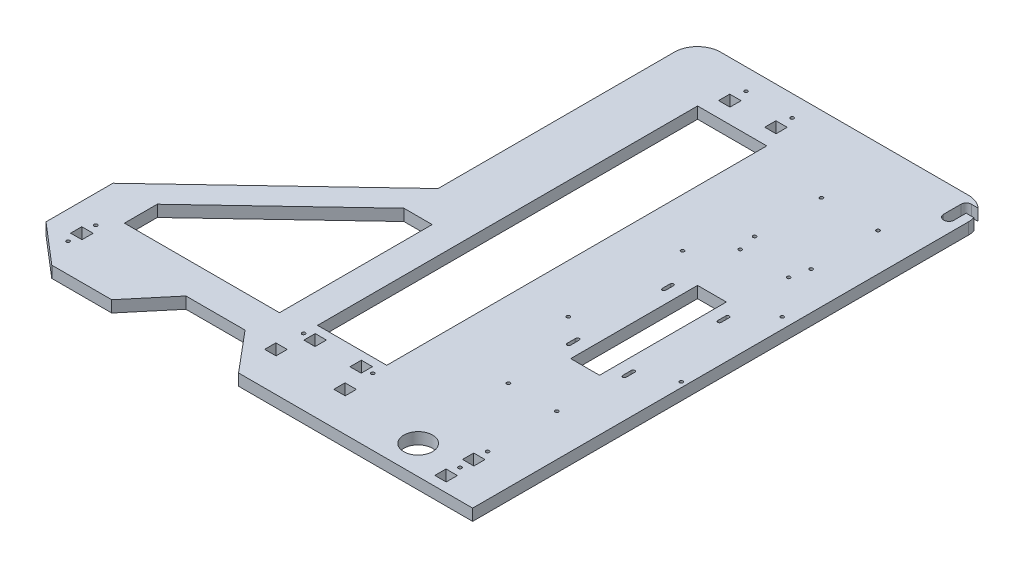
SolidWorks part; units mm, degrees
ref_plane "Front Plane" through (0, 0, 0) normal (0, 0, 1) x (1, 0, 0)
ref_plane "Top Plane" through (0, 0, 0) normal (0, 1, 0) x (1, 0, 0)
ref_plane "Right Plane" through (0, 0, 0) normal (1, 0, 0) x (0, 0, -1)
sketch "Sketch1" plane through (0, 0, 0) normal (0, 1, 0) x (1, 0, 0)
  line L0 (0, 0) -> (-235, 0)
  line L1 (-235, 0) -> (-235, -225)
  line L2 (-235, -225) -> (-380, -362)
  line L3 (-380, -362) -> (-380, -420)
  line L4 (-380, -420) -> (-345, -450)
  line L5 (-345, -450) -> (-293, -450)
  line L6 (-293, -450) -> (-263.6315, -415)
  line L7 (-263.6315, -415) -> (-212.3685, -415)
  line L8 (-212.3685, -415) -> (-183, -450)
  line L9 (-183, -450) -> (0, -450)
  line L10 (0, 0) -> (0, -450)
  line L12 (-293, -450) -> (-183, -450) construction
  dimension "D3" = 235
  dimension "D5" = 58
  dimension "D13" = 190
  dimension "D7" = 35
  dimension "D15" = 52
  dimension "D12" = 30
  dimension "D10" = 35
  dimension "D6" = 380
  dimension "D4" = 450
  dimension "D2" = 50
  dimension "D8" = 50
  dimension "D9" = 110
extrude "Boss-Extrude1" add sketch "Sketch1" along normal blind 10
sketch "Sketch16" plane through (0, 10, 0) normal (0, 1, 0) x (1, 0, 0)
  line L0 (0, -450) -> (20, -450)
  line L1 (20, -450) -> (20, 0)
  line L2 (20, 0) -> (0, 0)
  line L3 (0, 0) -> (0, -450)
  dimension "D1" = 20
  dimension "D2" = 90
extrude "Boss-Extrude2" add sketch "Sketch16" against normal through all
sketch "Sketch2" plane through (0, 10, 0) normal (0, 1, 0) x (1, 0, 0)
  line L0 (-235, -225) -> (-235, -415) construction
  line L1 (-263.6315, -415) -> (-212.3685, -415) construction
  line L2 (-345, -450) -> (-345, -328.931) construction
  line L3 (-235, -225) -> (-380, -362) construction
  line L4 (-345, -358.5097) -> (-235, -254.5787)
  line L5 (-235, -254.5787) -> (-210.5, -254.5787)
  line L6 (-210.5, -254.5787) -> (-210.5, -387)
  line L7 (-210.5, -387) -> (-345, -387)
  line L8 (-345, -387) -> (-345, -358.5097)
  line L9 (0, -450) -> (0, 0) construction
  line L10 (-184.5, -380) -> (-124.5, -380)
  line L11 (-184.5, -380) -> (-184.5, -50.425)
  line L12 (-184.5, -50.425) -> (-124.5, -50.425)
  line L13 (-124.5, -380) -> (-124.5, -50.425)
  line L14 (-124.5, -392.1) -> (-184.5, -392.1) construction
  line L15 (-16, -450) -> (-16, 0) construction
  line L16 (20, 0) -> (-235, 0) construction
  line L17 (-355.9, -440.6571) -> (-355.9, -339.2297) construction
  line L18 (-20.925, -441.85) -> (-11.075, -441.85)
  line L19 (-20.925, -441.85) -> (-20.925, -432.15)
  line L20 (-20.925, -432.15) -> (-11.075, -432.15)
  line L21 (-11.075, -441.85) -> (-11.075, -432.15)
  line L22 (-20.925, -441.85) -> (-11.075, -432.15) construction
  line L23 (-20.925, -432.15) -> (-11.075, -441.85) construction
  line L24 (-20.925, -417.85) -> (-11.075, -417.85)
  line L25 (-20.925, -417.85) -> (-20.925, -408.15)
  line L26 (-20.925, -408.15) -> (-11.075, -408.15)
  line L27 (-11.075, -417.85) -> (-11.075, -408.15)
  line L28 (-20.925, -417.85) -> (-11.075, -408.15) construction
  line L29 (-20.925, -408.15) -> (-11.075, -417.85) construction
  line L30 (-380, -420) -> (-345, -450) construction
  line L32 (-350.975, -408.15) -> (-360.825, -408.15)
  line L33 (-350.975, -408.15) -> (-350.975, -417.85)
  line L34 (-350.975, -417.85) -> (-360.825, -417.85)
  line L35 (-360.825, -408.15) -> (-360.825, -417.85)
  line L36 (-350.975, -408.15) -> (-360.825, -417.85) construction
  line L37 (-350.975, -417.85) -> (-360.825, -408.15) construction
  line L38 (-183, -450) -> (20, -450) construction
  line L39 (-183, -450) -> (20, -450) construction
  line L40 (-173.749, -32.425) -> (-113.749, -32.425) construction
  line L41 (-154.5, -50.425) -> (-154.5, -32.425) construction
  line L42 (-179.425, -27.575) -> (-169.575, -27.575)
  line L43 (-179.425, -27.575) -> (-179.425, -37.275)
  line L44 (-179.425, -37.275) -> (-169.575, -37.275)
  line L45 (-169.575, -27.575) -> (-169.575, -37.275)
  line L46 (-179.425, -27.575) -> (-169.575, -37.275) construction
  line L47 (-179.425, -37.275) -> (-169.575, -27.575) construction
  line L48 (-129.575, -37.275) -> (-139.425, -27.575) construction
  line L49 (-129.575, -27.575) -> (-139.425, -37.275) construction
  line L50 (-139.425, -27.575) -> (-139.425, -37.275)
  line L51 (-129.575, -37.275) -> (-139.425, -37.275)
  line L52 (-129.575, -27.575) -> (-129.575, -37.275)
  line L53 (-129.575, -27.575) -> (-139.425, -27.575)
  line L54 (-174.5, -32.425) -> (-174.5, -18.425) construction
  line L55 (-134.5, -32.425) -> (-134.5, -18.425) construction
  line L56 (-154.5, -380) -> (-154.5, -450) construction
  line L57 (-174.5, -392.1) -> (-134.5, -392.1) construction
  line L58 (-129.65, -397.025) -> (-139.35, -387.175) construction
  line L59 (-179.35, -387.175) -> (-169.65, -387.175)
  line L60 (-179.35, -387.175) -> (-179.35, -397.025)
  line L61 (-179.35, -397.025) -> (-169.65, -397.025)
  line L62 (-169.65, -387.175) -> (-169.65, -397.025)
  line L63 (-179.35, -387.175) -> (-169.65, -397.025) construction
  line L64 (-179.35, -397.025) -> (-169.65, -387.175) construction
  line L65 (-129.65, -387.175) -> (-139.35, -397.025) construction
  line L66 (-139.35, -387.175) -> (-139.35, -397.025)
  line L67 (-129.65, -397.025) -> (-139.35, -397.025)
  line L68 (-129.65, -387.175) -> (-129.65, -397.025)
  line L69 (-129.65, -387.175) -> (-139.35, -387.175)
  line L70 (-119.575, -420.95) -> (-129.425, -411.25) construction
  line L71 (-189.425, -411.25) -> (-179.575, -411.25)
  line L72 (-189.425, -411.25) -> (-189.425, -420.95)
  line L73 (-189.425, -420.95) -> (-179.575, -420.95)
  line L74 (-179.575, -411.25) -> (-179.575, -420.95)
  line L75 (-189.425, -411.25) -> (-179.575, -420.95) construction
  line L76 (-189.425, -420.95) -> (-179.575, -411.25) construction
  line L77 (-119.575, -411.25) -> (-129.425, -420.95) construction
  line L78 (-129.425, -411.25) -> (-129.425, -420.95)
  line L79 (-119.575, -420.95) -> (-129.425, -420.95)
  line L80 (-119.575, -411.25) -> (-119.575, -420.95)
  line L81 (-119.575, -411.25) -> (-129.425, -411.25)
  line L82 (-360.825, -408.15) -> (-11.075, -408.15) construction
  circle A0 centre (-16, -425) radius 1.45
  circle A1 centre (-16, -401) radius 1.45
  circle A2 centre (-355.9, -425) radius 1.45
  circle A3 centre (-355.9, -401) radius 1.45
  circle A4 centre (-174.5, -18.425) radius 1.45
  circle A5 centre (-134.5, -18.425) radius 1.45
  circle A6 centre (-124.5, -392.1) radius 1.45
  circle A7 centre (-184.5, -392.1) radius 1.45
  point P25 (-16, -437)
  point P30 (-16, -413)
  point P44 (-355.9, -413)
  point P61 (-174.5, -32.425)
  point P72 (-134.5, -32.425)
  point P85 (-174.5, -392.1)
  point P94 (-134.5, -392.1)
  point P95 (-184.5, -416.1)
  point P104 (-124.5, -416.1)
  point P105 (-154.5, -392.1)
  dimension "D13" = 2.9
  dimension "D14" = 2.9
  dimension "D23" = 2.9
  dimension "D24" = 2.9
  dimension "D31" = 2.9
  dimension "D37" = 2.9
  dimension "D1" = 21.5
  dimension "D2" = 28
  dimension "D3" = 24.5
  dimension "D4" = 60
  dimension "D7" = 26
  dimension "D8" = 9.7
  dimension "D9" = 9.85
  dimension "D10" = 9.85
  dimension "D11" = 9.7
  dimension "D12" = 24
  dimension "D15" = 24
  dimension "D19" = 9.85
  dimension "D20" = 9.7
  dimension "D26" = 12
  dimension "D27" = 9.85
  dimension "D28" = 9.7
  dimension "D33" = 9.7
  dimension "D38" = 9.85
  dimension "D39" = 9.7
  dimension "D41" = 24
  dimension "D34" = 30
  dimension "D36" = 12.1
  dimension "D30" = 18
  dimension "D29" = 40
  dimension "D17" = 13
  dimension "D32" = 14
  dimension "D35" = 20
  dimension "D16" = 12
  dimension "D21" = 90
  dimension "D25" = 24
  dimension "D5" = 359.75
  dimension "D22" = 349.75
  dimension "D40" = 30
  dimension "D6" = 70
  dimension "D42" = 0
  dimension "D43" = 0
  dimension "D18" = 16
  dimension "D44" = 9.85
extrude "Cut-Extrude1" cut sketch "Sketch2" against normal through all
fillet "Fillet1" radius 20 2 edges at (-235, 5, 0) (20, 5, 0)
sketch "Sketch11" plane through (0, 10, 0) normal (0, 1, 0) x (1, 0, 0)
  line L0 (-124.5, -215.2125) -> (20, -215.2125) construction
  line L1 (20, -450) -> (20, -20) construction
  line L3 (-52.25, -215.2125) -> (-52.25, -450) construction
  line L6 (-124.5, -380) -> (-124.5, -50.425) construction
  line L8 (-183, -450) -> (20, -450) construction
  circle A0 centre (-52.25, -425) radius 12.5
  circle A1 centre (-16, -425) radius 1.45 construction
  dimension "D1" = 25
  dimension "D2" = 0
  dimension "D3" = 0
extrude "WiringHole" cut sketch "Sketch11" against normal through all
sketch "Sketch9" [suppressed] plane through (0, 10, 0) normal (0, 1, 0) x (1, 0, 0)
  line L0 (-52.25, -402.5) -> (-52.25, 0) construction
  line L1 (0, 0) -> (-215, 0) construction
  line L2 (-124.5, -205.225) -> (20, -205.225) construction
  line L3 (-124.5, -365) -> (-124.5, -45.45) construction
  line L4 (-4.75, -116.725) -> (-4.75, -293.725) construction
  line L6 (-99.75, -116.725) -> (-4.75, -116.725) construction
  line L7 (-4.75, -293.725) -> (-99.75, -293.725) construction
  line L8 (-99.75, -293.725) -> (-99.75, -116.725) construction
  line L9 (20, -440) -> (20, -20) construction
  circle A0 centre (-52.25, -415) radius 12.5 construction
  circle A1 centre (-99.75, -116.725) radius 1.45
  circle A2 centre (-4.75, -116.725) radius 1.45
  circle A3 centre (-4.75, -293.725) radius 1.45
  circle A4 centre (-99.75, -293.725) radius 1.45
  dimension "D3" = 2.9
  dimension "D4" = 2.9
  dimension "D1" = 95
  dimension "D2" = 177
  dimension "D5" = 47.5
extrude "MountingHoles-PSU" [suppressed] cut sketch "Sketch9" against normal through all
sketch "Sketch10" plane through (0, 10, 0) normal (0, 1, 0) x (1, 0, 0)
  line L0 (-124.5, -215.2125) -> (20, -215.2125) construction
  line L1 (20, -450) -> (20, -20) construction
  line L2 (-49.75, -240.2125) -> (-24.75, -240.2125) construction
  line L3 (-37.25, -210.225) -> (-37.25, 0) construction
  line L4 (-52.25, -215.2125) -> (-52.25, -184.5972) construction
  line L7 (-124.5, -380) -> (-124.5, -50.425) construction
  line L8 (-49.75, -295.2125) -> (-24.75, -295.2125)
  line L9 (-49.75, -295.2125) -> (-49.75, -185.2125)
  line L10 (-49.75, -185.2125) -> (-24.75, -185.2125)
  line L11 (-24.75, -295.2125) -> (-24.75, -185.2125)
  line L12 (-49.75, -295.2125) -> (-24.75, -185.2125) construction
  line L13 (-49.75, -185.2125) -> (-24.75, -295.2125) construction
  line L15 (0, 0) -> (-215, 0) construction
  line L17 (-37.25, -210.225) -> (-37.25, -450) construction
  line L18 (-183, -450) -> (20, -450) construction
  line L19 (-64.75, -215.2125) -> (-39.75, -215.2125) construction
  line L20 (-37.25, -295.2125) -> (-37.25, -185.2125) construction
  dimension "D1" = 25
  dimension "D2" = 110
  dimension "D3" = 0
  dimension "D4" = 0
  dimension "D5" = 0
  dimension "D6" = 25
  dimension "D7" = 15
extrude "WiringSlot" cut sketch "Sketch10" against normal through all
sketch "CenterLines" plane through (0, 10, 0) normal (0, 1, 0) x (1, 0, 0)
  line L0 (-37.25, -295.2125) -> (-37.25, -185.2125) construction
  line L1 (-49.75, -295.2125) -> (-24.75, -295.2125) construction
  line L2 (-24.75, -185.2125) -> (-49.75, -185.2125) construction
  line L3 (-49.75, -240.2125) -> (-24.75, -240.2125) construction
  line L4 (-49.75, -185.2125) -> (-49.75, -295.2125) construction
  line L5 (-24.75, -295.2125) -> (-24.75, -185.2125) construction
ref_plane "Plane1" through (-37.25, 0, 0) normal (1, 0, 0) x (0, 0, -1)
sketch "Sketch6" plane through (0, 10, 0) normal (0, 1, 0) x (1, 0, 0)
  line L0 (-37.25, -295.2125) -> (-37.25, -185.2125) construction
  line L1 (-61.35, -240.2125) -> (-13.15, -240.2125) construction
  line L2 (-13.15, -195.7625) -> (-13.15, -278.2625) construction
  line L3 (-49.75, -295.2125) -> (-24.75, -295.2125) construction
  line L4 (-49.75, -240.2125) -> (-24.75, -240.2125) construction
  line L5 (-24.75, -185.2125) -> (-49.75, -185.2125) construction
  line L6 (-13.15, -195.7625) -> (-13.15, -202.7625) construction
  line L7 (-11.7, -195.7625) -> (-11.7, -202.7625)
  line L8 (-14.6, -195.7625) -> (-14.6, -202.7625)
  line L9 (-49.75, -240.2125) -> (-24.75, -240.2125) construction
  line L10 (-49.75, -185.2125) -> (-49.75, -295.2125) construction
  line L11 (-24.75, -295.2125) -> (-24.75, -185.2125) construction
  line L12 (-13.15, -285.2625) -> (-13.15, -278.2625) construction
  line L13 (-14.6, -285.2625) -> (-14.6, -278.2625)
  line L14 (-61.35, -277.6625) -> (-61.35, -202.7625) construction
  line L15 (-13.15, -285.2625) -> (-13.15, -202.7625) construction
  line L16 (-11.7, -285.2625) -> (-11.7, -278.2625)
  arc A2 (-11.7, -195.7625) -> (-14.6, -195.7625) centre (-13.15, -195.7625) ccw
  arc A3 (-14.6, -202.7625) -> (-11.7, -202.7625) centre (-13.15, -202.7625) ccw
  circle A4 centre (-61.35, -277.6625) radius 1.45
  circle A6 centre (-61.35, -202.7625) radius 1.45
  arc A8 (-14.6, -285.2625) -> (-11.7, -285.2625) centre (-13.15, -285.2625) ccw
  arc A9 (-11.7, -278.2625) -> (-14.6, -278.2625) centre (-13.15, -278.2625) ccw
  point P20 (-13.15, -199.2625)
  point P25 (-13.15, -281.7625)
  dimension "D6" = 0
  dimension "D8" = 2.9
  dimension "D12" = 2.9
  dimension "D4" = 1.45
  dimension "D5" = 1.45
  dimension "D11" = 82.5
  dimension "D14" = 74.9
  dimension "D2" = 24.1
  dimension "D3" = 48.2
  dimension "D9" = 7
  dimension "D10" = 7
extrude "MountingHoles-RAMPS" cut sketch "Sketch6" against normal through all
mirror "Mirror1" about plane through (-37.25, 0, 0) normal (1, 0, 0) of "MountingHoles-RAMPS"
sketch "Sketch5" plane through (0, 10, 0) normal (0, 1, 0) x (1, 0, 0)
  line L0 (-24.75, -240.2125) -> (-49.75, -240.2125) construction
  line L3 (-24.75, -295.2125) -> (-24.75, -185.2125) construction
  line L5 (-49.75, -185.2125) -> (-49.75, -295.2125) construction
  line L7 (-16.25, -139.7125) -> (-58.25, -139.7125) construction
  line L8 (-16.25, -340.7125) -> (-58.25, -340.7125) construction
  line L9 (-37.25, -240.2125) -> (-37.25, -139.7125) construction
  line L10 (-37.25, -240.2125) -> (-37.25, -340.7125) construction
  circle A0 centre (-58.25, -139.7125) radius 1.45
  circle A1 centre (-16.25, -139.7125) radius 1.45
  circle A2 centre (-16.25, -340.7125) radius 1.45
  circle A3 centre (-58.25, -340.7125) radius 1.45
  point P17 (-37.25, -139.7125)
  point P22 (-37.25, -340.7125)
  dimension "D2" = 2.9
  dimension "D5" = 2.9
  dimension "D6" = 2.9
  dimension "D7" = 2.9
  dimension "D3" = 201
  dimension "D4" = 100.5
  dimension "D8" = 21
  dimension "D9" = 21
  dimension "D10" = 100.5
extrude "MountingHoles-Melzi" cut sketch "Sketch5" against normal through all
sketch "Sketch13" plane through (0, 0, 0) normal (0, -1, 0) x (-1, 0, 0)
  line L0 (49.75, -215.2125) -> (124.5, -215.2125) construction
  line L1 (124.5, -380) -> (124.5, -50.425) construction
  line L2 (82.25, -264.7275) -> (82.25, -165.6975) construction
  line L3 (37.25, -295.2125) -> (37.25, -185.2125) construction
  line L4 (49.75, -185.2125) -> (49.75, -295.2125) construction
  line L6 (82.25, -264.7275) -> (-15.65, -264.7275) construction
  circle A0 centre (82.25, -165.6975) radius 1.45
  circle A1 centre (82.25, -264.7275) radius 1.45
  circle A2 centre (-10.59, -172.1775) radius 1.45
  circle A3 centre (-15.65, -264.7275) radius 1.45
  point P11 (82.25, -215.2125)
  dimension "D8" = 2.9
  dimension "D6" = 2.9
  dimension "D1" = 2.9
  dimension "D2" = 49.515
  dimension "D3" = 45
  dimension "D4" = 6.48
  dimension "D5" = 92.84
  dimension "D7" = 97.9
extrude "Mountingholes-Smoothieboard" cut sketch "Sketch13" against normal through all
mirror "Flipped" [suppressed] about plane through (-37.25, 0, 0) normal (1, 0, 0)
sketch "Sketch21" plane through (0, 10, 0) normal (0, 1, 0) x (1, 0, 0)
  line L0 (-37.25, -185.2125) -> (-37.25, 0) construction
  line L1 (-24.75, -185.2125) -> (-49.75, -185.2125) construction
  line L2 (0, 0) -> (-215, 0) construction
  line L3 (-37.25, -94.7125) -> (-23.3697, -94.7125) construction
  circle A0 centre (-12.75, -65.7125) radius 1.45
  circle A1 centre (-61.75, -65.7125) radius 1.45
  circle A2 centre (-61.75, -123.7125) radius 1.45
  circle A3 centre (-12.75, -123.7125) radius 1.45
  circle A4 centre (-16.25, -139.7125) radius 1.45 construction
  dimension "D1" = 2.9
  dimension "D2" = 24.5
  dimension "D3" = 29
  dimension "D4" = 45
extrude "Pi" cut sketch "Sketch21" against normal through all
sketch "Sketch17" plane through (0, 10, 0) normal (0, 1, 0) x (1, 0, 0)
  line L0 (0, 0) -> (20, 0) construction
  line L1 (20, -23.6361) -> (20, 0) construction
  line L2 (20, -450) -> (20, -20) construction
  line L3 (20, -10) -> (8, -10) construction
  line L4 (20, -14.5) -> (8, -14.5)
  line L5 (20, -5.5) -> (8, -5.5)
  arc A0 (20, -14.5) -> (20, -5.5) centre (20, -10) ccw
  arc A1 (8, -5.5) -> (8, -14.5) centre (8, -10) ccw
  point P8 (14, -10)
  dimension "D1" = 9
  dimension "D2" = 12
  dimension "D3" = 10
extrude "Cut-Extrude3" cut sketch "Sketch17" against normal through all
sketch "Sketch18" plane through (0, 10, 0) normal (0, 1, 0) x (1, 0, 0)
  line L0 (8, -5.5) -> (8, -14.5) construction
  line L1 (3.5, -10) -> (8, -10) construction
  line L2 (8, -10) -> (8, -25) construction
  line L3 (12.5, -10) -> (12.5, -25)
  line L4 (3.5, -10) -> (3.5, -25)
  arc A0 (8, -5.5) -> (8, -14.5) centre (8, -10) ccw construction
  arc A1 (12.5, -10) -> (3.5, -10) centre (8, -10) ccw
  arc A2 (3.5, -25) -> (12.5, -25) centre (8, -25) ccw
  point P10 (8, -17.5)
  dimension "D1" = 9
  dimension "D2" = 0
  dimension "D3" = 15
extrude "Cut-Extrude4" cut sketch "Sketch18" against normal through all
sketch "Sketch19" plane through (0, 10, 0) normal (0, 1, 0) x (1, 0, 0)
  line L0 (-2, -25) -> (18, -25) construction
  line L1 (8, -25) -> (8, -5.5) construction
  circle A0 centre (18, -25) radius 1.45
  arc A1 (8, -5.5) -> (3.5, -10) centre (8, -10) ccw construction
  circle A2 centre (-2, -25) radius 1.45
  dimension "D2" = 2.9
extrude "Cut-Extrude5" [suppressed] cut sketch "Sketch19" against normal through all
equation "\"Y-ROD-SPACING\"=75"
equation "\"Y-BED-OFFSET\"=2"
equation "\"Y-BED-ROD-INSET\"=3.5"
equation "\"T-SLOT-NUT-FILLET-RADIUS\"=0.5"
equation "\"T-SLOT-SCREW-SHAFT-RADIUS\"=1.55"
equation "\"T-SLOT-SCREW-SHAFT-CUTOUT-LENGTH\"=11"
equation "\"T-SLOT-NUT-DEPTH\"=3.5"
equation "\"T-SLOT-NUT-WIDTH\"=2.85"
equation "\"T-SLOT-NUT-END-DISTANCE\"=8"
equation "\"ACRYLIC-TAB-CUTOUT-SIZE\"=\"ACRYLIC-THICKNESS\"+\"ACRYLIC-TAB-TOLERANCE\"*2"
equation "\"ACRYLIC-TAB-WIDTH\"=\"ACRYLIC-THICKNESS\""
equation "\"ACRYLIC-M3-HOLE\"=2.9"
equation "\"SMOOTHROD-CAP-SCREW-DISTANCE\"=20"
equation "\"FRAME-WIDTH-INNER\"=370"
equation "\"D24@Sketch2\"=\"ACRYLIC-M3-HOLE\""
equation "\"D23@Sketch2\"=\"ACRYLIC-M3-HOLE\""
equation "\"D19@Sketch2\"=\"ACRYLIC-THICKNESS\"-\"KERF\"*2"
equation "\"D20@Sketch2\"=\"ACRYLIC-TAB-WIDTH\"-\"KERF\"*4"
equation "\"D37@Sketch2\"=\"ACRYLIC-M3-HOLE\""
equation "\"D33@Sketch2\"=\"ACRYLIC-TAB-WIDTH\"-\"KERF\"*4"
equation "\"D38@Sketch2\"=\"ACRYLIC-THICKNESS\"-\"KERF\"*2"
equation "\"D39@Sketch2\"=\"ACRYLIC-TAB-WIDTH\"-\"KERF\"*4"
equation "\"D13@Sketch2\"=\"ACRYLIC-M3-HOLE\""
equation "\"D14@Sketch2\"=\"ACRYLIC-M3-HOLE\""
equation "\"D8@Sketch2\"=\"ACRYLIC-TAB-WIDTH\"-\"KERF\"*4"
equation "\"D9@Sketch2\"=\"ACRYLIC-THICKNESS\"-\"KERF\"*2"
equation "\"D10@Sketch2\"=\"ACRYLIC-THICKNESS\"-\"KERF\"*2"
equation "\"D11@Sketch2\"=\"ACRYLIC-TAB-WIDTH\"-\"KERF\"*4"
equation "\"D31@Sketch2\"=\"ACRYLIC-M3-HOLE\""
equation "\"D27@Sketch2\"=\"ACRYLIC-THICKNESS\"-\"KERF\"*2"
equation "\"D28@Sketch2\"=\"ACRYLIC-TAB-WIDTH\"-\"KERF\"*4"
equation "\"NEMA17-HOLE-SPACING\"=31"
equation "\"NEMA17-CENTRAL-CUTOUT\"=22.5"
equation "\"Z-BRACKET-REACH\"=55"
equation "\"TOP-BRACKET-SPACING\"=40"
equation "\"D29@Sketch2\"=\"TOP-BRACKET-SPACING\""
equation "\"ACRYLIC-THICKNESS\"=10"
equation "\"SMOOTHROD-Z-LENGTH\"=350"
equation "\"D5@Sketch2\"=\"SMOOTHROD-Z-LENGTH\"-\"SMOOTHROD-TIGHTENING-HEADROOM\"+10"
equation "\"SMOOTHROD-X-LENGTH\"=350"
equation "\"SMOOTHROD-Y-LENGTH\"=350"
equation "\"D22@Sketch2\"=\"SMOOTHROD-Y-LENGTH\"-\"SMOOTHROD-TIGHTENING-HEADROOM\""
equation "\"SMOOTHROD-TIGHTENING-HEADROOM\"=.25"
equation "\"X-ROD-SPACING\"=45"
equation "\"Z-ROD-SPACING\"=17.5"
equation "\"LEADSCREW-Z-LENGTH\"=300"
equation "\"SCREW-HEAD-RADIUS\"=6"
equation "\"PRINTED-X-SMOOTHROD-DIAMETER\"=8.8"
equation "\"PRINTED-X-SMOOTHROD-CUTOUT\"=10"
equation "\"PRINTED-X-BASE-HEIGHT\"=10"
equation "\"PRINTED-LM8UU-CUTOUT-SIZE\"=15.5"
equation "\"PRINTED-LM8UU-CUTOUT-LENGTH\"=24.5"
equation "\"PRINTED-X-IDLER-HEIGHT\"=16"
equation "\"PSU-MOUNTING-WIDTH\"=95"
equation "\"PSU-MOUNTING-HEIGHT\"=177"
equation "\"D1@Sketch9\"=\"PSU-MOUNTING-WIDTH\""
equation "\"D3@Sketch9\"=\"ACRYLIC-M3-HOLE\""
equation "\"D1@Boss-Extrude1\"=\"ACRYLIC-THICKNESS\""
equation "\"D6@Sketch1\"=\"SMOOTHROD-Y-LENGTH\"+30"
equation "\"D4@Sketch9\"=\"ACRYLIC-M3-HOLE\""
equation "\"D2@Sketch9\"=\"PSU-MOUNTING-HEIGHT\""
equation "\"D5@Sketch9\"=\"PSU-MOUNTING-WIDTH\"/2"
equation "\"D4@Sketch1\"=\"SMOOTHROD-Z-LENGTH\"+100"
equation "\"D8@Sketch6\"=\"ACRYLIC-M3-HOLE\""
equation "\"D12@Sketch6\"=\"ACRYLIC-M3-HOLE\""
equation "\"D2@Sketch5\"=\"ACRYLIC-M3-HOLE\""
equation "\"D5@Sketch5\"=\"ACRYLIC-M3-HOLE\""
equation "\"D6@Sketch5\"=\"ACRYLIC-M3-HOLE\""
equation "\"D7@Sketch5\"=\"ACRYLIC-M3-HOLE\""
equation "\"D1@Sketch13\"=\"ACRYLIC-M3-HOLE\""
equation "\"D6@Sketch13\"=\"ACRYLIC-M3-HOLE\""
equation "\"D8@Sketch13\"=\"ACRYLIC-M3-HOLE\""
equation "\"D4@Sketch6\"=\"ACRYLIC-M3-HOLE\"/2"
equation "\"D5@Sketch6\"=\"ACRYLIC-M3-HOLE\"/2"
equation "\"Y-BED-SCREW-SPACING\"=209"
equation "\"Y-BED-SCREW-CUTOUT-SLOT-HEIGHT\"=2"
equation "\"ACRYLIC-THICKNESS2\"=4.5"
equation "\"ACRYLIC-TAB-TOLERANCE\"=-.05"
equation "\"Z-ROD-INSET\"=13.5"
equation "\"SCREW-LENGTH-FRAME\"=\"ACRYLIC-THICKNESS\" + 10"
equation "\"SCREW-LENGTH-MOTOR\"=\"ACRYLIC-THICKNESS\" + 5"
equation "\"SCREW-LENGTH-EXTRUDER\"=28"
equation "\"Y-BELT-TO-ROD-DISTANCE\"=20"
equation "\"SPOOL-HOLDER-ROD-SPACING\"=150"
equation "\"ACRYLIC-X-CARRIAGE-WIDTH\"=55"
equation "\"ACRYLIC-X-CARRIAGE-HEIGHT\"=75"
equation "\"ACRYLIC-X-CARRIAGE-LM8UU-CUTOUT-WIDTH\"=24.25"
equation "\"ACRYLIC-X-CARRIAGE-SCREW-SPACING-X\"=15"
equation "\"ACRYLIC-X-CARRIAGE-SCREW-SPACING-Y\"=33"
equation "\"ACRYLIC-X-CARRIAGE-CENTER-TAB-SPACING\"=14"
equation "\"ACRYLIC-X-CARRIAGE-EXTRUDER-OFFSET\"=26"
equation "\"ACRYLIC-X-CARRIAGE-EXTRUDER-ANGLE\"=90"
equation "\"ACRYLIC-X-CARRIAGE-EXTRUDER-SHELF-DEPTH\"=\"ACRYLIC-X-CARRIAGE-EXTRUDER-OFFSET\" + 28"
equation "\"ACRYLIC-X-CARRIAGE-EXTRUDER-BRACE-SPACING\"=23"
equation "\"ACRYLIC-X-CARRIAGE-EXTRUDER-BRACE-TAB-OFFSET\"=20"
equation "\"ACRYLIC-X-CARRIAGE-EXTRUDER-BRACE-HEIGHT\"=35"
equation "\"ACRYLIC-X-CARRIAGE-EXTRUDER-BRACE-SCREW-SPACING\"=22"
equation "\"D1@Sketch19\"=\"SMOOTHROD-CAP-SCREW-DISTANCE\"/2"
equation "\"D2@Sketch19\"=\"ACRYLIC-M3-HOLE\""
equation "\"D1@Sketch21\"=\"ACRYLIC-M3-HOLE\""
equation "\"KERF\"=0.075"
equation "\"PRINTED-M3-HOLE\"=3.5"
equation "\"PRINTED-M3-NUT-AF\"=6.25"
equation "\"ACRYLIC-X-CARRIAGE-LM8UU-CUTOUT-HEIGHT\"=11.0"
equation "\"ACRYLIC-X-CARRIAGE-DUAL-WIDTH-MULTIPLIER\"=1.65"
equation "\"ACRYLIC-X-CARRIAGE-DUAL-HOTEND-SPACING\"=42"
equation "\"ACRYLIC-X-CARRIAGE-DUAL-WIDTH\"=75"
equation "\"ACRYLIC-X-CARRIAGE-DUAL-FAN-OFFSET\"=52"
equation "\"ACRYLIC-X-CARRIAGE-DUAL-FAN-HEIGHT\"=20"
equation "\"ACRYLIC-X-CARRIAGE-DUAL-HOTEND-SEPARATION\"=36"
equation "\"ACRYLIC-X-CARRIAGE-DUAL-MOUNT-PLATE-DEPTH\"=75"
equation "\"ACRYLIC-X-CARRIAGE-DUAL-MOUNT-BRACE-WIDTH\"=33"
equation "\"ACRYLIC-X-CARRIAGE-DUAL-MOUNT-SCREW-WIDTH\"=40"
equation "\"BLOWER-FAN-WIDTH\"=15"
equation "\"D44@Sketch2\"=\"ACRYLIC-THICKNESS\"-\"KERF\"*2"
